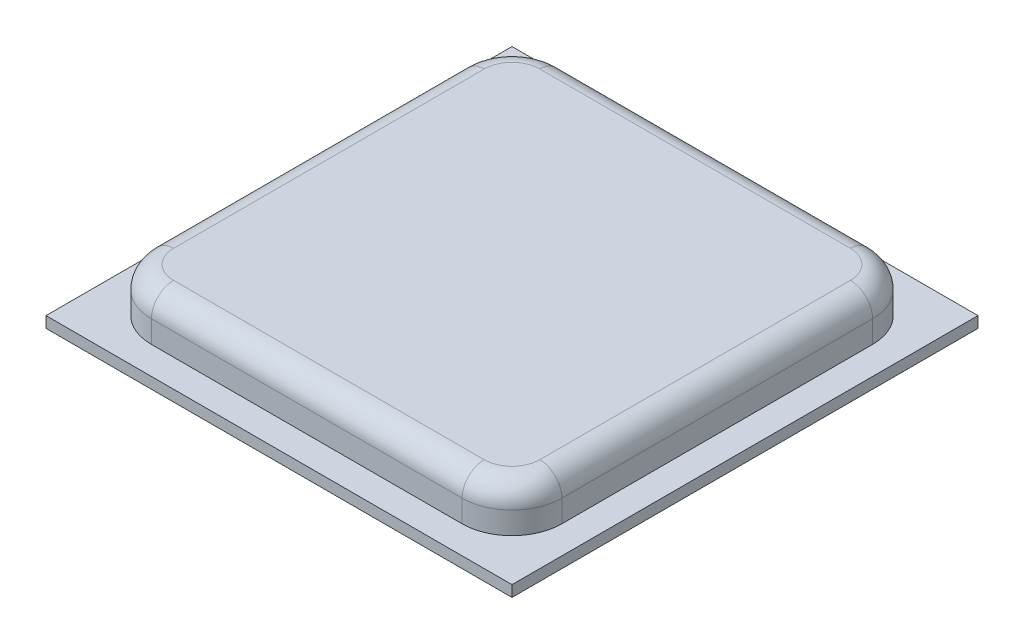
SolidWorks part; units mm, degrees
ref_plane "Front Plane" through (0, 0, 0) normal (0, 0, 1) x (1, 0, 0)
ref_plane "Top Plane" through (0, 0, 0) normal (0, 1, 0) x (1, 0, 0)
ref_plane "Right Plane" through (0, 0, 0) normal (1, 0, 0) x (0, 0, -1)
sketch "Sketch1" plane through (0, 0, 0) normal (0, 1, 0) x (1, 0, 0)
  line L1 (-14, -18.5) -> (14, -18.5)
  line L2 (-18.5, -14) -> (-18.5, 14)
  line L3 (-14, 18.5) -> (14, 18.5)
  line L4 (18.5, -14) -> (18.5, 14)
  line L5 (-18.5, -18.5) -> (18.5, 18.5) construction
  line L6 (-18.5, 18.5) -> (18.5, -18.5) construction
  line L7 (21, -21) -> (-21, -21)
  line L8 (21, -21) -> (21, 21)
  line L9 (21, 21) -> (-21, 21)
  line L10 (-21, -21) -> (-21, 21)
  line L11 (21, -21) -> (-21, 21) construction
  line L12 (21, 21) -> (-21, -21) construction
  arc A0 (-14, 18.5) -> (-18.5, 14) centre (-14, 14) ccw
  arc A1 (-18.5, -14) -> (-14, -18.5) centre (-14, -14) ccw
  arc A2 (18.5, -14) -> (14, -18.5) centre (14, -14) cw
  arc A3 (18.5, 14) -> (14, 18.5) centre (14, 14) ccw
  point P0 (0, 0)
  point P18 (0, 0)
  dimension "D3" = 4.5
  dimension "D1" = 37
  dimension "D2" = 37
  dimension "D4" = 42
  dimension "D5" = 42
extrude "Boss-Extrude1" add sketch "Sketch1" along normal blind 1
extrude "Boss-Extrude2" add sketch "Sketch1<2>" along normal blind 5 contours L4 A3 L3 A0 L2 A1 L1 A2 region at (0, 0, 0)
sketch "Sketch1<2>" plane through (0, 0, 0) normal (0, 1, 0) x (1, 0, 0) same geometry as "Sketch1"
fillet "Fillet1" radius 2 8 edges at (17.182, 5, 17.182) (0, 5, 18.5) (-17.182, 5, 17.182) (-18.5, 5, 0) (-17.182, 5, -17.182) (0, 5, -18.5) (17.182, 5, -17.182) (18.5, 5, 0)
